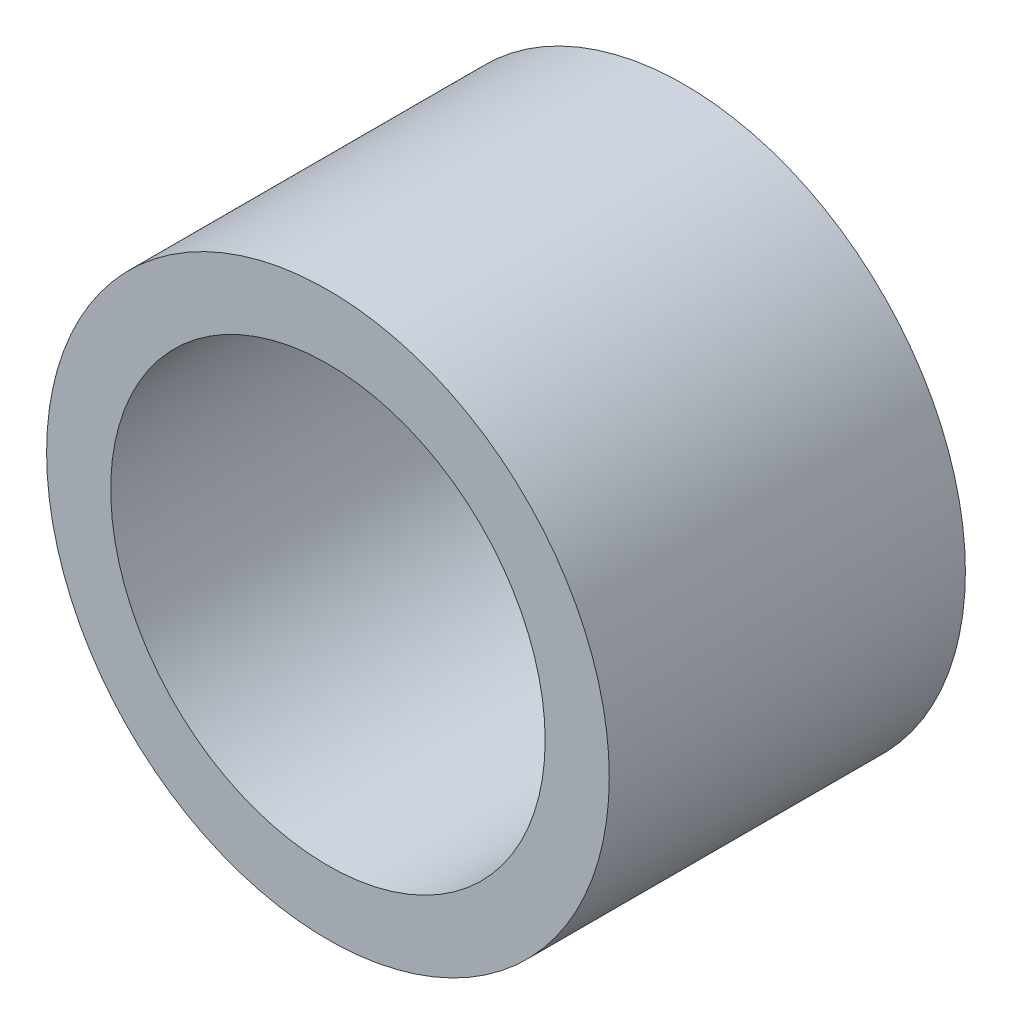
SolidWorks part; units mm, degrees
ref_plane "前视基准面" through (0, 0, 0) normal (0, 0, 1) x (1, 0, 0)
ref_plane "上视基准面" through (0, 0, 0) normal (0, 1, 0) x (1, 0, 0)
ref_plane "右视基准面" through (0, 0, 0) normal (1, 0, 0) x (0, 0, -1)
sketch "草图1" plane through (0, 0, 0) normal (0, 0, 1) x (1, 0, 0)
  circle A0 centre (0, 0) radius 3.95
  circle A1 centre (0, 0) radius 3.05
  dimension "D1" = 7.9
  dimension "D2" = 6.1
extrude "凸台-拉伸1" add sketch "草图1" along normal blind 2.5 and the other way blind 2.5
